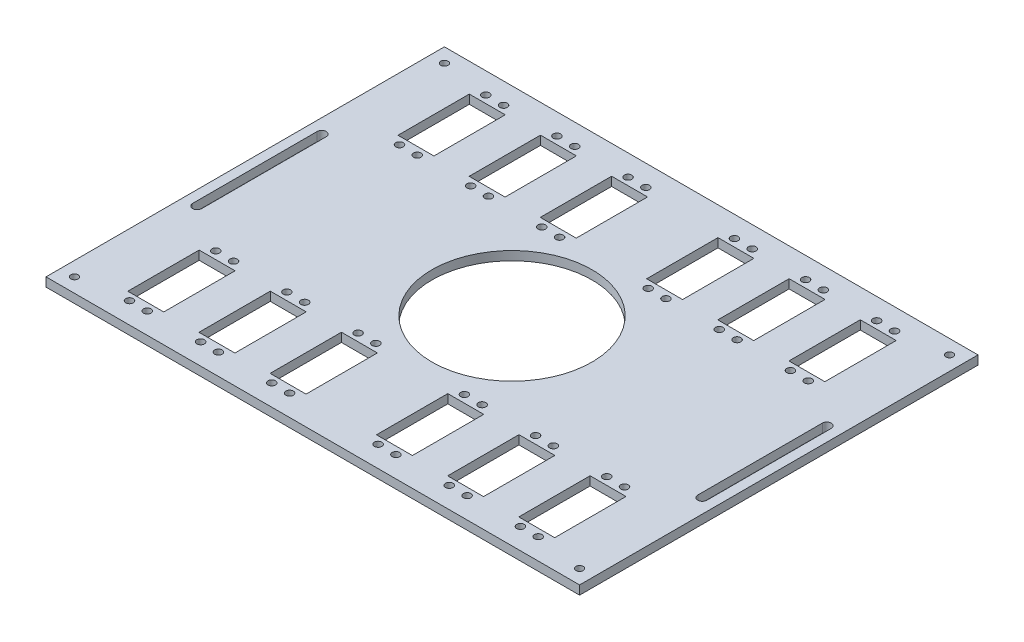
SolidWorks part; units mm, degrees
note: The reader was unsure of these and kept them because the rebuilt part matched: shared geometry of "Sketch1<5>", "Sketch1<6>".
ref_plane "Front Plane" through (0, 0, 0) normal (0, 0, 1) x (1, 0, 0)
ref_plane "Top Plane" through (0, 0, 0) normal (0, 1, 0) x (1, 0, 0)
ref_plane "Right Plane" through (0, 0, 0) normal (1, 0, 0) x (0, 0, -1)
sketch "Sketch1" plane through (0, 0, 0) normal (0, 1, 0) x (1, 0, 0)
  line L0 (0, 0) -> (115.4519, 0) construction
  line L1 (0, 0) -> (0, 69.5335) construction
  line L2 (-150, 112) -> (-116.8238, 78.8238) construction
  line L3 (150, -112) -> (-150, -112)
  line L4 (150, -112) -> (150, 112)
  line L5 (150, 112) -> (-150, 112)
  line L6 (-150, -112) -> (-150, 112)
  line L7 (150, -112) -> (-150, 112) construction
  line L8 (150, 112) -> (-150, -112) construction
  line L9 (-120, 96) -> (-99.8, 96)
  line L10 (-120, 96) -> (-120, 55.9)
  line L11 (-120, 55.9) -> (-99.8, 55.9)
  line L12 (-99.8, 96) -> (-99.8, 55.9)
  circle A0 centre (-142, 104) radius 2.05
  circle A1 centre (-114.9, 100.1557) radius 2.1
  circle A2 centre (-104.9, 100.1557) radius 2.1
  circle A3 centre (-104.9, 51.6557) radius 2.1
  circle A4 centre (-114.9, 51.6557) radius 2.1
  point P1 (0, 0)
  dimension "D4" = 4.1
  dimension "D6" = 4.2
  dimension "D1" = 300
  dimension "D2" = 224
  dimension "D3" = 45
  dimension "D5" = 8
  dimension "D7" = 20.2
  dimension "D8" = 40.1
  dimension "D9" = 4.1557
  dimension "D10" = 10
  dimension "D11" = 5.1
  dimension "D12" = 10
  dimension "D13" = 4.2443
  dimension "D14" = 5.1
  dimension "D15" = 16
  dimension "D16" = 30
extrude "Boss-Extrude2" add sketch "Sketch1" along normal blind 5 contours L12 L9 L10 L11 | A1 | A3 | A4 | L6 L3 L4 L5 A4 A3 A2 A1 A0 L9 L12 L11 L10
extrude "Cut-Extrude1" cut sketch "Sketch1<5>" along normal up to next contours L12 L9 L10 L11 | A2 | A1 | A4 | A3
sketch "Sketch1<5>" plane through (0, 0, 0) normal (0, 1, 0) x (1, 0, 0) same geometry as "Sketch1"
pattern_linear "LPattern1" count 3 spacing 40 along (1, 0, 0) of "Cut-Extrude1"
mirror "Mirror1" about plane through (0, 0, 0) normal (0, 0, 1) of "LPattern1", "Cut-Extrude1" second plane through (0, 0, 0) second plane normal (1, 0, 0)
extrude "Cut-Extrude3" cut sketch "Sketch1<6>" along normal up to next contours A0
sketch "Sketch1<6>" plane through (0, 0, 0) normal (0, 1, 0) x (1, 0, 0) same geometry as "Sketch1"
mirror "Mirror2" about plane through (0, 0, 0) normal (1, 0, 0) of "Cut-Extrude3" second plane through (0, 0, 0) second plane normal (0, 0, 1)
sketch "Sketch2" plane through (0, 5, 0) normal (0, 1, 0) x (1, 0, 0)
  circle A0 centre (0, 0) radius 45
  dimension "D1" = 90
extrude "Cut-Extrude4" cut sketch "Sketch2" against normal up to next
sketch "Sketch3" plane through (0, 5, 0) normal (0, 1, 0) x (1, 0, 0)
  line L0 (-142, -35) -> (-142, 35) construction
  line L1 (-144.55, -35) -> (-144.55, 35)
  line L2 (-139.45, -35) -> (-139.45, 35)
  line L3 (-150, -112) -> (-150, 112) construction
  line L4 (0, 0) -> (0, 28.7231) construction
  line L5 (142, -35) -> (142, 35) construction
  line L6 (144.55, -35) -> (144.55, 35)
  line L7 (139.45, -35) -> (139.45, 35)
  line L8 (0, -200000) -> (0, 200069.5335) construction
  arc A0 (-144.55, -35) -> (-139.45, -35) centre (-142, -35) ccw
  arc A1 (-139.45, 35) -> (-144.55, 35) centre (-142, 35) ccw
  arc A2 (144.55, -35) -> (139.45, -35) centre (142, -35) cw
  arc A3 (139.45, 35) -> (144.55, 35) centre (142, 35) cw
  point P2 (-142, 0)
  point P15 (142, 0)
  dimension "D3" = 2.55
  dimension "D1" = 8
  dimension "D2" = 70
extrude "Cut-Extrude5" cut sketch "Sketch3" against normal blind 10
